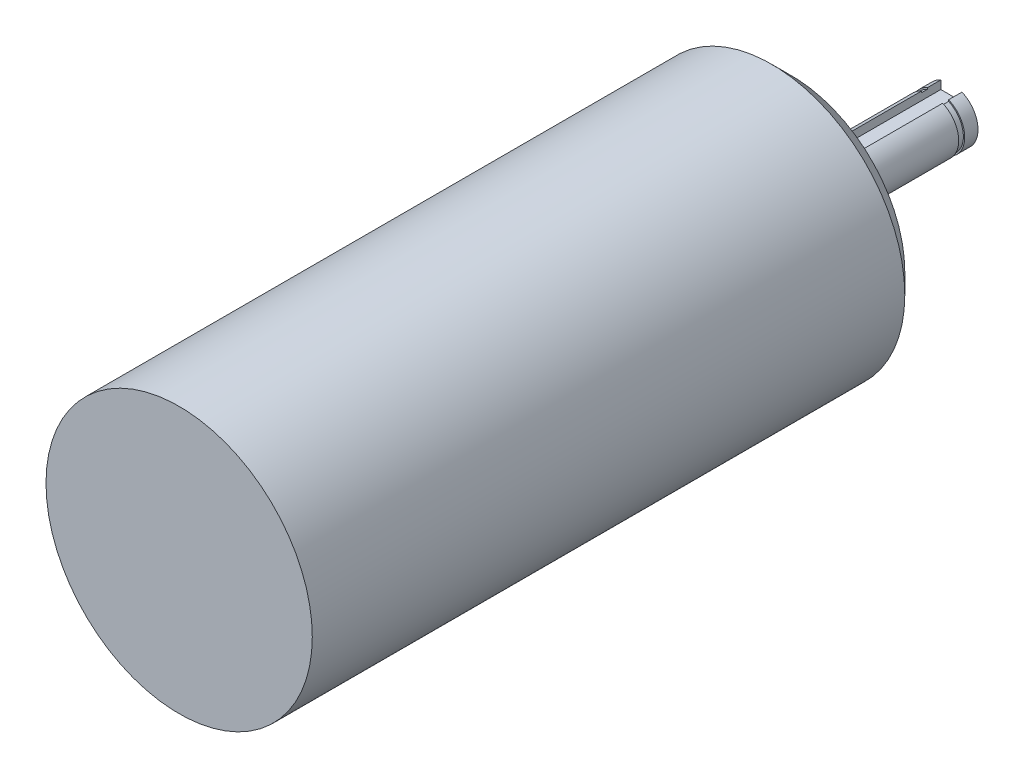
SolidWorks part; units mm, degrees
ref_plane "Front Plane" through (0, 0, 0) normal (0, 0, 1) x (1, 0, 0)
ref_plane "Top Plane" through (0, 0, 0) normal (0, 1, 0) x (1, 0, 0)
ref_plane "Right Plane" through (0, 0, 0) normal (1, 0, 0) x (0, 0, -1)
sketch "Sketch1" plane through (0, 0, 0) normal (0, 0, 1) x (1, 0, 0)
  circle A0 centre (0, 0) radius 20
  dimension "D1" = 40
extrude "Boss-Extrude1" add sketch "Sketch1" along normal blind 92
sketch "face mounting holes" plane through (0, 0, 0) normal (0, 0, -1) x (-1, 0, 0)
  point P0 (0, 12.5)
  point P4 (12.5, 0)
  point P5 (0, -12.5)
  point P6 (-12.5, 0)
  point P7 (0, 0)
  dimension "D2" = 25
  dimension "D1" = 4
hole_wizard "M4x0.7 Tapped Hole1" positions "Sketch3" profile "Sketch5" tap size "M4x0.7" standard "ANSI Metric"
sketch "Sketch3" plane through (0, 0, 0) normal (0, 0, -1) x (-1, 0, 0)
  point P0 (0, 12.5)
  point P3 (-12.5, 0)
  point P6 (0, -12.5)
  point P9 (12.5, 0)
sketch "Sketch5" plane through (0, 12.5, 0) normal (1, 0, 0) x (0, 1, 0)
  line L0 (0, 0) -> (0, 4.9914)
  line L1 (0, 4.9914) -> (1.65, 4)
  line L2 (1.65, 4) -> (1.65, 0.375)
  line L3 (1.65, 0.375) -> (2.025, 0)
  line L5 (2.025, 0) -> (0, 0)
  line L6 (-1.65, 0.375) -> (-2.025, 0) construction
  line L10 (0, 4.9914) -> (-1.65, 4) construction
  line L11 (0, -6.35) -> (0, 107.95) construction
  dimension "Tap Drill Dia." = 3.3
  dimension "Tap Drill Depth" = 4
  dimension "Near C'Sink Dia." = 4.05
  dimension "Near C'Sink Angle" = 90
  dimension "Drill Angle" = 118
cosmetic thread "Hole Thread1" parameters "D1"=4, "D2"=4
cosmetic thread "Hole Thread2" parameters "D1"=4, "D2"=4
cosmetic thread "Hole Thread3" parameters "D1"=4, "D2"=4
cosmetic thread "Hole Thread4" parameters "D1"=4, "D2"=4
sketch "Sketch6" plane through (0, 0, 0) normal (0, 0, -1) x (-1, 0, 0)
  circle A0 centre (0, 0) radius 4
  dimension "D1" = 8
extrude "Boss-Extrude2" add sketch "Sketch6" along normal blind 24
chamfer "Chamfer1" distance 3 angle 45 1 edges at (20, 0, 0)
sketch "Sketch7" plane through (0, 0, -24) normal (0, 0, -1) x (-1, 0, 0)
  line L1 (-1.5875, 2.4125) -> (1.5875, 2.4125)
  line L2 (-1.5875, 2.4125) -> (-1.5875, 5.5875)
  line L3 (-1.5875, 5.5875) -> (1.5875, 5.5875)
  line L4 (1.5875, 2.4125) -> (1.5875, 5.5875)
  line L5 (-1.5875, 2.4125) -> (1.5875, 5.5875) construction
  line L6 (-1.5875, 5.5875) -> (1.5875, 2.4125) construction
  circle A0 centre (0, 0) radius 4 construction
  point P0 (0, 4)
  dimension "D1" = 3.175
  dimension "D2" = 3.175
extrude "Cut-Extrude1" cut sketch "Sketch7" against normal blind 19
ref_plane "Plane1" through (0, 0, -22) normal (0, 0, -1) x (-1, 0, 0)
sketch "Sketch8" plane through (0, 0, -22) normal (0, 0, -1) x (-1, 0, 0)
  circle A0 centre (0, 0) radius 3.8
  circle A1 centre (0, 0) radius 4
  arc A2 (-1.5875, 3.6715) -> (1.5875, 3.6715) centre (0, 0) ccw construction
  dimension "D1" = 7.6
extrude "Cut-Extrude2" cut sketch "Sketch8" against normal blind 0.9
equation "\"D1@Sketch7\"=0.125in"
equation "\"D2@Sketch7\"=0.125in"
